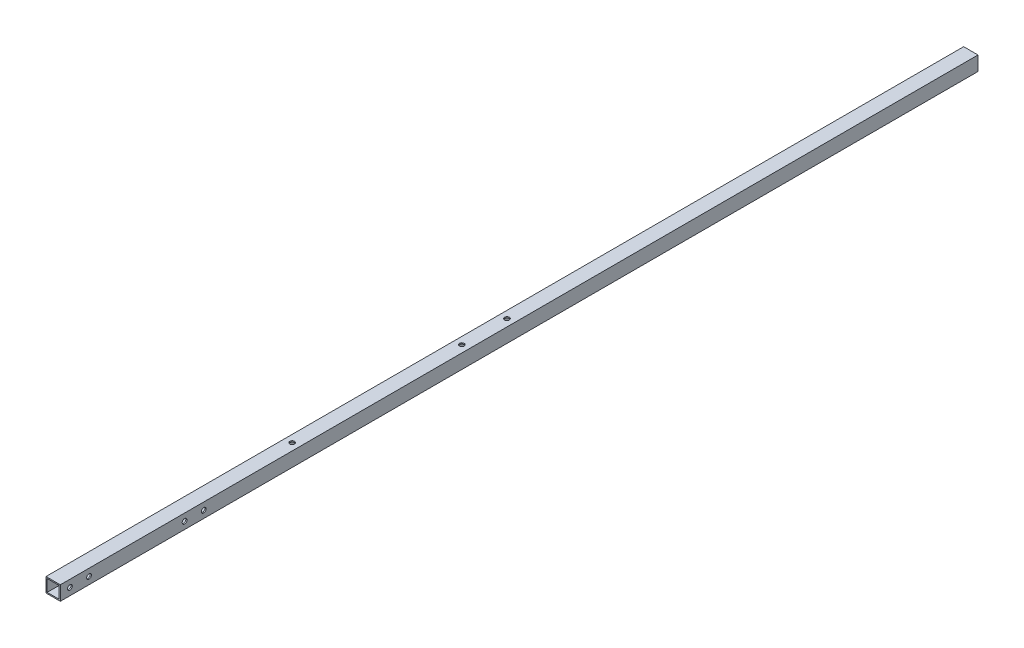
SolidWorks part; units mm, degrees
material "6061 Alloy"
ref_plane "Front Plane" through (0, 0, 0) normal (0, 0, 1) x (1, 0, 0)
ref_plane "Top Plane" through (0, 0, 0) normal (0, 1, 0) x (1, 0, 0)
ref_plane "Right Plane" through (0, 0, 0) normal (1, 0, 0) x (0, 0, -1)
sketch "Sketch1" plane through (0, 0, 0) normal (0, 0, 1) x (1, 0, 0)
  line L1 (-7.9375, -7.9375) -> (7.9375, -7.9375)
  line L2 (-7.9375, -7.9375) -> (-7.9375, 7.9375)
  line L3 (-7.9375, 7.9375) -> (7.9375, 7.9375)
  line L4 (7.9375, -7.9375) -> (7.9375, 7.9375)
  line L5 (-7.9375, -7.9375) -> (7.9375, 7.9375) construction
  line L6 (-7.9375, 7.9375) -> (7.9375, -7.9375) construction
  line L7 (-9.525, -9.525) -> (9.525, -9.525)
  line L8 (-9.525, -9.525) -> (-9.525, 9.525)
  line L9 (-9.525, 9.525) -> (9.525, 9.525)
  line L10 (9.525, -9.525) -> (9.525, 9.525)
  line L11 (-9.525, -9.525) -> (9.525, 9.525) construction
  line L12 (-9.525, 9.525) -> (9.525, -9.525) construction
  point P0 (0, 0)
  point P6 (0, 0)
  dimension "D1" = 19.05
  dimension "D2" = 19.05
  dimension "D3" = 1.5875
  dimension "D4" = 1.5875
extrude "Boss-Extrude1" add sketch "Sketch1" along normal mid plane 1219.2
sketch "Sketch3" plane through (9.525, 0, 0) normal (1, 0, 0) x (0, 0, -1)
  line L0 (-609.6, 0) -> (-596.9, 0) construction
  line L1 (-609.6, -9.525) -> (-609.6, 9.525) construction
  line L2 (-609.6, 0) -> (-571.5, 0) construction
  circle A0 centre (-571.5, 0) radius 3.175
  circle A1 centre (-596.9, 0) radius 3.175
extrude "Cut-Extrude1" cut sketch "Sketch3" against normal through all
sketch "Sketch4" plane through (-9.525, 0, 0) normal (-1, 0, 0) x (0, 0, 1)
  line L0 (419.1, 0) -> (609.6, 0) construction
  line L1 (609.6, 0) -> (444.5, 0) construction
  line L3 (609.6, 9.525) -> (609.6, -9.525) construction
  circle A0 centre (444.5, 0) radius 3.175
  circle A1 centre (419.1, 0) radius 3.175
extrude "Cut-Extrude2" cut sketch "Sketch4" against normal through all
sketch "Sketch7" plane through (0, -9.525, 0) normal (0, -1, 0) x (1, 0, 0)
  line L0 (0, 609.6) -> (0, 292.1) construction
  line L1 (0, 609.6) -> (0, 66.675) construction
  circle A0 centre (0, 292.1) radius 3.175
  circle A1 centre (0, 66.675) radius 3.175
extrude "Cut-Extrude4" cut sketch "Sketch7" against normal through all and the other way through all
sketch "Sketch8" plane through (0, 9.525, 0) normal (0, 1, 0) x (1, 0, 0)
  line L0 (0, -66.675) -> (0, -6.675) construction
  circle A0 centre (0, -6.675) radius 3.175
extrude "Cut-Extrude5" cut sketch "Sketch8" against normal through all
